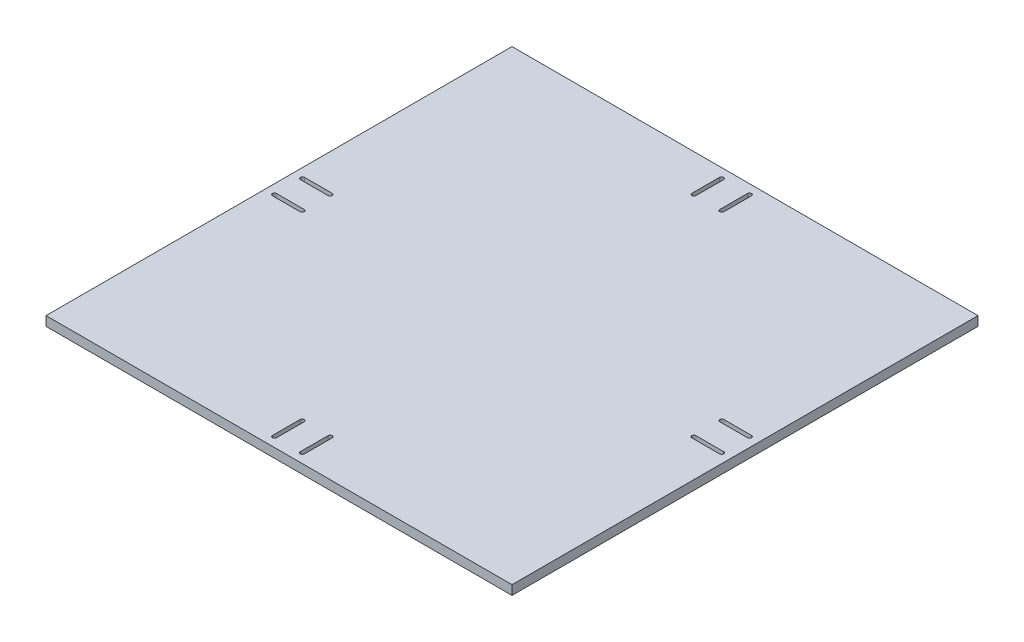
SolidWorks part; units mm, degrees
ref_plane "Plano frontal" through (0, 0, 0) normal (0, 0, 1) x (1, 0, 0)
ref_plane "Plano superior" through (0, 0, 0) normal (0, 1, 0) x (1, 0, 0)
ref_plane "Plano direito" through (0, 0, 0) normal (1, 0, 0) x (0, 0, -1)
sketch "Esboço1" plane through (0, 0, 0) normal (0, 1, 0) x (1, 0, 0)
  line L1 (0, 0) -> (500, 0)
  line L2 (0, 0) -> (0, 500)
  line L3 (0, 500) -> (500, 500)
  line L4 (500, 0) -> (500, 500)
  dimension "D1" = 500
extrude "Ressalto-extrusão1" add sketch "Esboço1" along normal blind 10
sketch "Esboço2" plane through (0, 10, 0) normal (0, 1, 0) x (1, 0, 0)
  line L0 (500, 500) -> (0, 500) construction
  line L1 (232.85, 489.85) -> (232.85, 460.15)
  line L2 (237.15, 489.85) -> (237.15, 460.15)
  line L3 (262.85, 489.85) -> (262.85, 460.15)
  line L4 (267.15, 489.85) -> (267.15, 460.15)
  line L29 (489.85, 267.15) -> (460.15, 267.15)
  line L30 (489.85, 262.85) -> (460.15, 262.85)
  line L31 (489.85, 237.15) -> (460.15, 237.15)
  line L32 (489.85, 232.85) -> (460.15, 232.85)
  line L33 (267.15, 10.15) -> (267.15, 39.85)
  line L34 (262.85, 10.15) -> (262.85, 39.85)
  line L35 (237.15, 10.15) -> (237.15, 39.85)
  line L36 (232.85, 10.15) -> (232.85, 39.85)
  line L37 (10.15, 232.85) -> (39.85, 232.85)
  line L38 (10.15, 237.15) -> (39.85, 237.15)
  line L39 (10.15, 262.85) -> (39.85, 262.85)
  line L40 (10.15, 267.15) -> (39.85, 267.15)
  arc A0 (237.15, 489.85) -> (232.85, 489.85) centre (235, 489.85) ccw
  arc A1 (232.85, 460.15) -> (237.15, 460.15) centre (235, 460.15) ccw
  arc A2 (267.15, 489.85) -> (262.85, 489.85) centre (265, 489.85) ccw
  arc A3 (262.85, 460.15) -> (267.15, 460.15) centre (265, 460.15) ccw
  arc A20 (489.85, 262.85) -> (489.85, 267.15) centre (489.85, 265) ccw
  arc A21 (460.15, 267.15) -> (460.15, 262.85) centre (460.15, 265) ccw
  arc A22 (489.85, 232.85) -> (489.85, 237.15) centre (489.85, 235) ccw
  arc A23 (460.15, 237.15) -> (460.15, 232.85) centre (460.15, 235) ccw
  arc A24 (262.85, 10.15) -> (267.15, 10.15) centre (265, 10.15) ccw
  arc A25 (267.15, 39.85) -> (262.85, 39.85) centre (265, 39.85) ccw
  arc A26 (232.85, 10.15) -> (237.15, 10.15) centre (235, 10.15) ccw
  arc A27 (237.15, 39.85) -> (232.85, 39.85) centre (235, 39.85) ccw
  arc A28 (10.15, 237.15) -> (10.15, 232.85) centre (10.15, 235) ccw
  arc A29 (39.85, 232.85) -> (39.85, 237.15) centre (39.85, 235) ccw
  arc A30 (10.15, 267.15) -> (10.15, 262.85) centre (10.15, 265) ccw
  arc A31 (39.85, 262.85) -> (39.85, 267.15) centre (39.85, 265) ccw
  point P17 (250, 500)
  point P64 (250, 250)
  dimension "D1" = 4.3
  dimension "D3" = 4.3
  dimension "D2" = 10.15
  dimension "D4" = 29.7
  dimension "D5" = 30
  dimension "D6" = 15
  dimension "D7" = 4
extrude "Corte-extrusão2" cut sketch "Esboço2" against normal through all both
